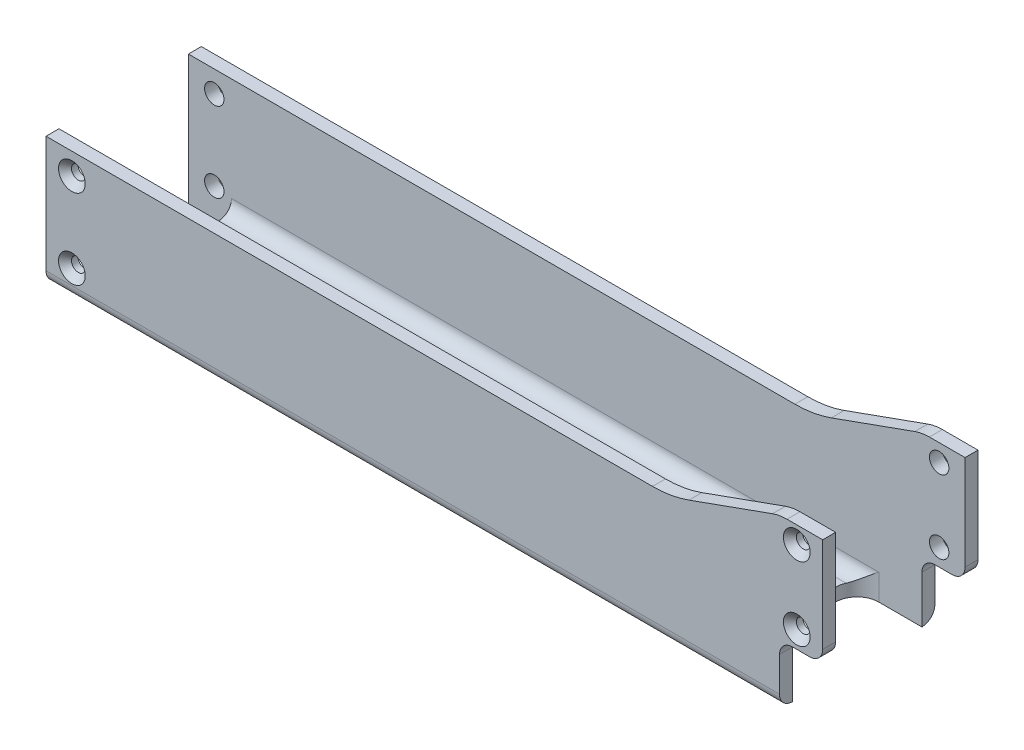
SolidWorks part; units mm, degrees
ref_plane "Front Plane" through (0, 0, 0) normal (0, 0, 1) x (1, 0, 0)
ref_plane "Top Plane" through (0, 0, 0) normal (0, 1, 0) x (1, 0, 0)
ref_plane "Right Plane" through (0, 0, 0) normal (1, 0, 0) x (0, 0, -1)
sketch "Sketch1" plane through (0, 0, 0) normal (0, 0, 1) x (1, 0, 0)
  line L0 (52.7874, 245.1803) -> (193.3525, 245.1803)
  line L4 (52.7874, 245.1803) -> (52.7874, 215.1803)
  line L5 (52.7874, 215.1803) -> (222.7874, 215.1803)
  line L6 (222.7874, 245.1803) -> (222.7874, 215.1803) construction
  line L7 (222.7874, 215.1803) -> (222.7874, 254.1811)
  line L8 (222.7874, 254.1811) -> (201.7956, 246.6492)
  line L9 (241.0832, 254.1811) -> (222.7874, 254.1811) construction
  arc A0 (201.7956, 246.6492) -> (193.3525, 245.1803) centre (193.3525, 270.1803) cw
extrude "Boss-Extrude1" add sketch "Sketch1" against normal blind 3
sketch "Sketch3" plane through (0, 0, -36) normal (0, 0, -1) x (-1, 0, 0)
  line L4 (-222.7874, 254.1811) -> (-222.7874, 215.1803)
  line L5 (-222.7874, 254.1811) -> (-222.7874, 215.1803)
  line L6 (-52.7874, 215.1803) -> (-52.7874, 245.1803)
  line L7 (-52.7874, 245.1803) -> (-193.3525, 245.1803)
  line L9 (-201.7956, 246.6492) -> (-222.7874, 254.1811)
  line L10 (-201.7956, 246.6492) -> (-222.7874, 254.1811)
  line L11 (-222.7874, 215.1803) -> (-52.7874, 215.1803)
  line L12 (-52.7874, 215.1803) -> (-52.7874, 245.1803)
  line L13 (-52.7874, 245.1803) -> (-193.3525, 245.1803)
  line L17 (-222.7874, 215.1803) -> (-52.7874, 215.1803)
  arc A1 (-201.7956, 246.6492) -> (-193.3525, 245.1803) centre (-193.3525, 270.1803) ccw
  arc A2 (-201.7956, 246.6492) -> (-193.3525, 245.1803) centre (-193.3525, 270.1803) ccw
  dimension "D1" = 0
extrude "Boss-Extrude2" add sketch "Sketch3" against normal blind 3 separate body
sketch "Sketch4" plane through (0, 0, -3) normal (0, 0, -1) x (-1, 0, 0)
  line L1 (-52.7874, 215.1803) -> (-207.7874, 215.1803)
  line L2 (-52.7874, 215.1803) -> (-52.7874, 218.1803)
  line L3 (-52.7874, 218.1803) -> (-207.7874, 218.1803)
  line L4 (-207.7874, 215.1803) -> (-207.7874, 218.1803)
extrude "Boss-Extrude3" add sketch "Sketch4" along normal up to surface (30 mm away) up to face at (157.7268, 236.8645, -33)
fillet "Fillet1" radius 5 2 edges at (207.7874, 216.6803, -33) (207.7874, 216.6803, -3)
ref_plane "Plane1" through (130.2874, 0, 0) normal (1, 0, 0) x (0, 0, -1)
fillet "Fillet2" radius 3 4 edges at (132.7874, 218.1803, -3) (132.7874, 218.1803, -33) (137.7874, 215.1803, 0) (137.7874, 215.1803, -36)
sketch "Sketch5" plane through (0, 218.1803, 0) normal (0, 1, 0) x (1, 0, 0)
  line L0 (52.7874, 33) -> (193.3525, 33) construction
  line L1 (52.7874, 3) -> (62.7874, 3)
  line L2 (52.7874, 3) -> (52.7874, 33)
  line L3 (52.7874, 33) -> (62.7874, 33)
  line L4 (62.7874, 3) -> (62.7874, 33)
extrude "Cut-Extrude1" cut sketch "Sketch5" against normal through all both and the other way through all
sketch "Sketch6" plane through (0, 0, 0) normal (0, 0, 1) x (1, 0, 0)
  line L0 (62.7877, 245.1806) -> (62.7877, 215.1806) construction
  line L1 (54.7876, 222.1805) -> (54.7876, 245.1805) construction
  line L2 (62.7877, 245.1806) -> (62.7877, 215.1806) construction
  line L3 (54.7876, 222.1805) -> (54.7876, 245.1805) construction
  line L4 (54.7876, 245.1805) -> (62.7877, 245.1806) construction
  line L5 (58.7876, 245.1805) -> (58.7876, 215.1803) construction
  line L6 (52.7874, 215.1803) -> (62.7874, 215.1803) construction
  circle A0 centre (58.7876, 240.1805) radius 1.6
  circle A1 centre (58.7876, 221.6803) radius 1.6
extrude "Cut-Extrude2" cut sketch "Sketch6" against normal blind 4
sketch "Sketch7" plane through (222.7874, 0, 0) normal (1, 0, 0) x (0, 0, -1)
  line L0 (0, 218.1803) -> (0, 254.1811) construction
  line L1 (3, 254.1811) -> (0, 254.1811)
  line L2 (3, 254.1811) -> (3, 229.1811)
  line L3 (3, 229.1811) -> (0, 229.1811)
  line L4 (0, 254.1811) -> (0, 229.1811)
  line L5 (36, 254.1811) -> (36, 218.1803) construction
  line L6 (33, 254.1811) -> (36, 254.1811)
  line L7 (33, 254.1811) -> (33, 229.1811)
  line L8 (33, 229.1811) -> (36, 229.1811)
  line L9 (36, 254.1811) -> (36, 229.1811)
extrude "Boss-Extrude4" add sketch "Sketch7" along normal blind 10
fillet "Fillet3" radius 3 4 edges at (222.7874, 229.1811, -34.5) (222.7874, 229.1811, -1.5) (232.7874, 229.1811, -34.5) (232.7874, 229.1811, -1.5)
sketch "Sketch9" plane through (0, 0, 0) normal (0, 0, 1) x (1, 0, 0)
  line L0 (230.7874, 254.1811) -> (230.7874, 229.3173) construction
  line L1 (230.7874, 254.1811) -> (230.7874, 229.3173) construction
  line L2 (222.7874, 226.1811) -> (222.7874, 254.1811) construction
  line L3 (222.7874, 226.1811) -> (222.7874, 254.1811) construction
  line L4 (222.7874, 254.1811) -> (230.7874, 254.1811) construction
  line L5 (226.7874, 254.1811) -> (226.7874, 229.1811) construction
  circle A0 centre (226.7874, 250.1811) radius 1.6
  circle A1 centre (226.7874, 233.1811) radius 1.6
extrude "Cut-Extrude3" cut sketch "Sketch9" against normal blind 5
sketch "Sketch10" plane through (0, 0, -36) normal (0, 0, -1) x (-1, 0, 0)
  circle A0 centre (-226.7874, 250.1811) radius 2.25
  circle A1 centre (-226.7874, 233.1811) radius 2.25
  circle A2 centre (-58.7876, 240.1805) radius 2.25
  circle A3 centre (-58.7876, 221.6803) radius 2.25
extrude "Cut-Extrude4" cut sketch "Sketch10" against normal blind 3
chamfer "Chamfer1" distance 1.5 angle 45 4 edges at (60.3876, 240.1805, 0) (60.3876, 221.6803, 0) (228.3874, 250.1811, 0) (228.3874, 233.1811, 0)
fillet "Fillet4" radius 10 2 edges at (222.7874, 254.1811, -34.5) (222.7874, 254.1811, -1.5)
